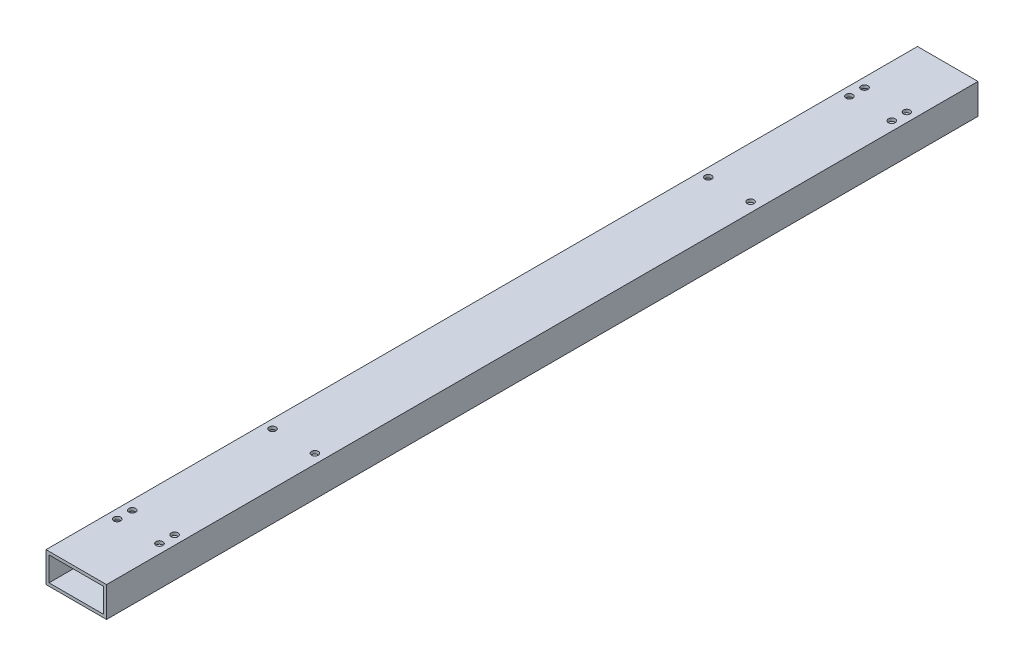
SolidWorks part; units mm, degrees
ref_plane "Front Plane" through (0, 0, 0) normal (0, 0, 1) x (1, 0, 0)
ref_plane "Top Plane" through (0, 0, 0) normal (0, 1, 0) x (1, 0, 0)
ref_plane "Right Plane" through (0, 0, 0) normal (1, 0, 0) x (0, 0, -1)
sketch "Sketch1" plane through (0, 0, 0) normal (0, 0, 1) x (1, 0, 0)
  line L0 (31.75, 0) -> (28.575, 0) construction
  line L1 (-31.75, 0) -> (31.75, 0) construction
  line L2 (0, 15.875) -> (0, -15.875)
  point P7 (0, 0)
  dimension "Width" = 63.5
  dimension "Wall Thickness" = 3.175
  dimension "Height" = 31.75
sketch "Sketch2" plane through (0, 0, 0) normal (1, 0, 0) x (0, 0, -1)
  line L0 (457.2, 0) -> (-457.2, 0)
  point P4 (0, 0)
  dimension "Length" = 914.4
sketch "Sketch3" plane through (0, 0, 0) normal (0, 0, 1) x (1, 0, 0)
  line L0 (0, 12.7) -> (0, 15.875) construction
  line L1 (-31.75, 15.875) -> (31.75, 15.875)
  line L2 (-31.75, 15.875) -> (-31.75, -15.875)
  line L3 (-31.75, -15.875) -> (31.75, -15.875)
  line L4 (31.75, 15.875) -> (31.75, -15.875)
  line L5 (-31.75, 15.875) -> (31.75, -15.875) construction
  line L6 (-31.75, -15.875) -> (31.75, 15.875) construction
  line L7 (-28.575, 12.7) -> (28.575, 12.7)
  line L8 (-28.575, 12.7) -> (-28.575, -12.7)
  line L9 (-28.575, -12.7) -> (28.575, -12.7)
  line L10 (28.575, 12.7) -> (28.575, -12.7)
  line L11 (-28.575, 12.7) -> (28.575, -12.7) construction
  line L12 (-28.575, -12.7) -> (28.575, 12.7) construction
  line L13 (31.75, 0) -> (28.575, 0) construction
  line L14 (31.75, 0) -> (28.575, 0) construction
  point P0 (0, 0)
  point P8 (0, 0)
extrude "Boss-Extrude1" add sketch "Sketch3" along normal up to vertex (457.2 mm away) and the other way up to vertex (457.2 mm away) up to point (0, 0, 457.2) other way up to point (0, 0, -457.2)
sketch "Sketch4" plane through (0, 0, 0) normal (0, 0, 1) x (1, 0, 0)
  line L0 (31.75, -15.875) -> (28.575, -15.875) construction
  line L1 (31.75, -15.875) -> (31.75, 15.875) construction
  line L2 (28.575, -12.7) -> (28.575, 12.7) construction
  line L3 (-31.75, -15.875) -> (31.75, -15.875) construction
sketch "Sketch5" plane through (0, -15.875, 0) normal (0, -1, 0) x (1, 0, 0)
  line L1 (-28.575, 384.175) -> (28.575, 384.175)
  line L2 (-28.575, 384.175) -> (-28.575, 400.05)
  line L3 (-28.575, 400.05) -> (28.575, 400.05)
  line L4 (28.575, 384.175) -> (28.575, 400.05)
  line L5 (-28.575, 384.175) -> (28.575, 400.05) construction
  line L6 (-28.575, 400.05) -> (28.575, 384.175) construction
  line L7 (-31.75, 457.2) -> (31.75, 457.2) construction
  line L8 (-31.75, 0) -> (31.75, 0) construction
  line L9 (-31.75, 457.2) -> (-31.75, -457.2) construction
  line L10 (31.75, 457.2) -> (31.75, -457.2) construction
  circle A0 centre (-22.225, 392.1125) radius 3.5719
  circle A1 centre (22.225, 392.1125) radius 3.5719
  circle A2 centre (22.225, -392.1125) radius 3.5719
  circle A3 centre (-22.225, -392.1125) radius 3.5719
  circle A4 centre (22.225, 376.2375) radius 3.5719
  circle A5 centre (-22.225, 376.2375) radius 3.5719
  circle A6 centre (22.225, -376.2375) radius 3.5719
  circle A7 centre (-22.225, -376.2375) radius 3.5719
  point P0 (0, 392.1125)
  dimension "D3" = 7.1437
  dimension "D4" = 7.1437
  dimension "D1" = 57.15
  dimension "D2" = 15.875
  dimension "D5" = 22.225
  dimension "D6" = 22.225
  dimension "D7" = 44.45
  dimension "D8" = 57.15
  dimension "D9" = 15.875
extrude "Cut-Extrude1" cut sketch "Sketch5" against normal through all contours A0 | A1 | A3 | A2 | A7 | A6 | A4 | A5
sketch "Sketch6" plane through (-31.75, 0, 0) normal (-1, 0, 0) x (0, 0, 1)
  circle A0 centre (0, 0) radius 6.35
  dimension "D1" = 12.7
sketch "Sketch7" plane through (0, 15.875, 0) normal (0, 1, 0) x (1, 0, 0)
  line L0 (0, 493.1857) -> (0, -485.0339)
  line L1 (-303.9468, 4.0759) -> (319.0859, 4.0759)
sketch "Sketch8" plane through (0, 15.875, 0) normal (0, 1, 0) x (1, 0, 0)
  line L0 (-22.6771, 228.6) -> (21.7729, 228.6) construction
  line L2 (31.75, 0) -> (-31.75, 0) construction
  line L3 (-31.75, -457.2) -> (-31.75, 457.2) construction
  circle A0 centre (21.7729, 228.6) radius 3.5725
  circle A1 centre (-22.6771, 228.6) radius 3.5725
  circle A2 centre (21.7729, -228.6) radius 3.5725
  circle A3 centre (-22.6771, -228.6) radius 3.5725
  point P3 (-0.4521, 228.6)
  point P11 (0, 0)
  dimension "D1" = 7.145
  dimension "D2" = 7.145
  dimension "D3" = 44.45
  dimension "D4" = 228.6
extrude "Cut-Extrude2" cut sketch "Sketch8" against normal through all
